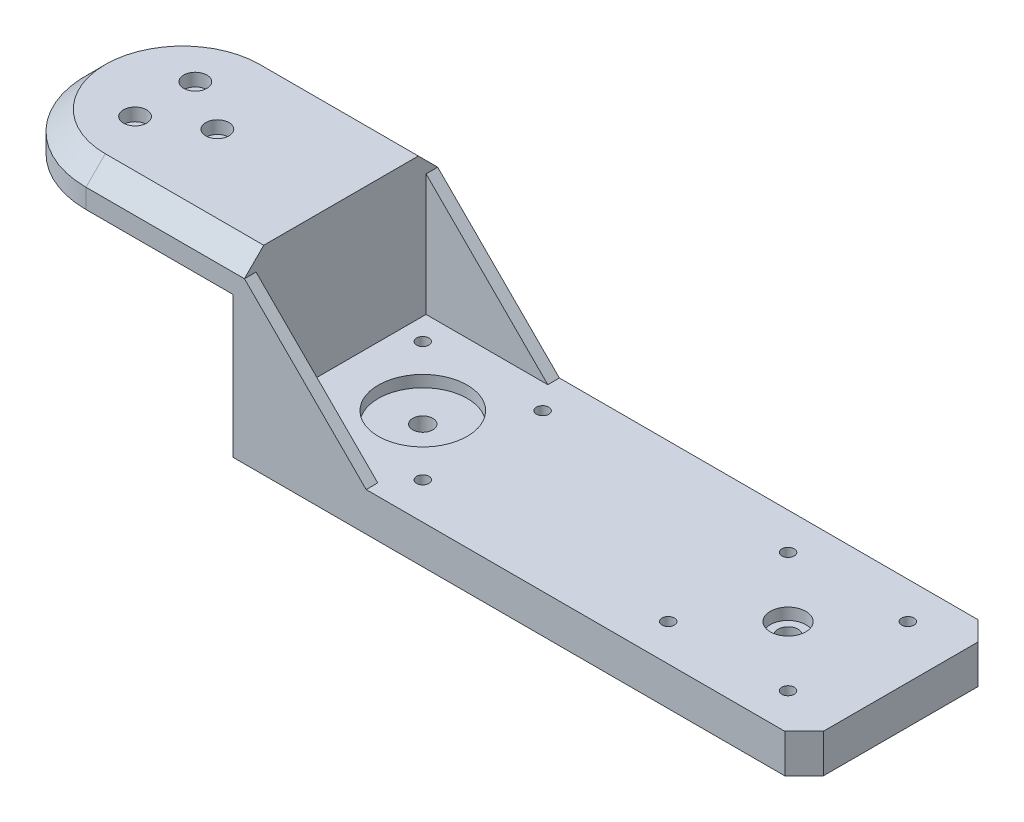
SolidWorks part; units mm, degrees
ref_plane "前视基准面" through (0, 0, 0) normal (0, 0, 1) x (1, 0, 0)
ref_plane "上视基准面" through (0, 0, 0) normal (0, 1, 0) x (1, 0, 0)
ref_plane "右视基准面" through (0, 0, 0) normal (1, 0, 0) x (0, 0, -1)
other "Configuration Table"
sketch "草图1" plane through (0, 0, 0) normal (0, 1, 0) x (1, 0, 0)
  line L0 (0, 0) -> (9, 0) construction
  circle A0 centre (0, 0) radius 12.4
  circle A1 centre (9, 0) radius 1.6
  circle A2 centre (-4.5, -7.7942) radius 1.6
  circle A3 centre (-4.5, 7.7942) radius 1.6
  dimension "D1" = 24.8
  dimension "D2" = 3.2
  dimension "D5" = 9
  dimension "D4" = 3
extrude "凸台-拉伸1" add sketch "草图1" along normal blind 19.5
sketch "草图4" plane through (0, 19.5, 0) normal (0, 1, 0) x (1, 0, 0)
  line L0 (0, 25) -> (33, 25)
  line L1 (33, 25) -> (33, -25)
  line L2 (33, -25) -> (0, -25)
  arc A0 (0, 25) -> (0, -25) centre (0, 0) ccw
  circle A1 centre (0, 0) radius 12.4
  circle A2 centre (0, 0) radius 12.4 construction
  dimension "D1" = 50
  dimension "D2" = 33
extrude "凸台-拉伸3" add sketch "草图4" against normal blind 10
sketch "草图5" plane through (33, 0, 0) normal (1, 0, 0) x (0, 0, -1)
  line L1 (-25, 19.5) -> (25, 19.5)
  line L2 (-25, 19.5) -> (-25, -17)
  line L3 (-25, -17) -> (25, -17)
  line L4 (25, 19.5) -> (25, -17)
  dimension "D1" = 36.5
extrude "凸台-拉伸4" add sketch "草图5" along normal blind 8
sketch "草图6" plane through (0, -17, 0) normal (0, -1, 0) x (1, 0, 0)
  line L0 (41, 25) -> (41, -25) construction
  line L1 (33, 25) -> (185.81, 25)
  line L2 (33, 25) -> (33, -25)
  line L3 (33, -25) -> (185.81, -25)
  line L5 (46.65, 15.5) -> (77.65, 15.5) construction
  line L6 (46.65, 15.5) -> (46.65, -15.5) construction
  line L7 (62.15, 0) -> (62.15, 25) construction
  line L8 (185.81, 25) -> (185.81, -25)
  line L9 (46.65, 15.5) -> (141.16, 15.5) construction
  circle A1 centre (62.15, 0) radius 2.6
  circle A2 centre (156.66, 0) radius 2.6
  circle A3 centre (46.65, 15.5) radius 1.6
  circle A4 centre (77.65, 15.5) radius 1.6
  circle A5 centre (77.65, -15.5) radius 1.6
  circle A6 centre (46.65, -15.5) radius 1.6
  circle A7 centre (141.16, 15.5) radius 1.6
  circle A8 centre (172.16, 15.5) radius 1.6
  circle A9 centre (172.16, -15.5) radius 1.6
  circle A10 centre (141.16, -15.5) radius 1.6
  dimension "D2" = 5.2
  dimension "D3" = 21.15
  dimension "D8" = 15.5
  dimension "D9" = 3.2
  dimension "D10" = 5.2
  dimension "D11" = 94.51
  dimension "D14" = 13.65
  dimension "D6" = 31
  dimension "D7" = 31
  dimension "D13" = 94.51
  dimension "D4" = 2
  dimension "D5" = 2
  dimension "D12" = 2
extrude "凸台-拉伸5" add sketch "草图6" along normal blind 10
sketch "草图7" plane through (0, -17, 0) normal (0, 1, 0) x (1, 0, 0)
  circle A0 centre (156.66, 0) radius 4.6
  circle A1 centre (156.66, 0) radius 2.6 construction
  dimension "D1" = 9.2
extrude "切除-拉伸1" cut sketch "草图7" against normal blind 3
chamfer "倒角2" distance 5 angle 45 3 edges at (20.5, 19.5, -25) (20.5, 19.5, 25) (-25, 19.5, 0)
sketch "草图9" plane through (0, 0, 25) normal (0, 0, 1) x (1, 0, 0)
  line L0 (41, 14.5) -> (72.5, -17)
  line L1 (185.81, -17) -> (41, -17) construction
  line L2 (72.5, -17) -> (41, -17)
  line L3 (41, -17) -> (41, 14.5)
  dimension "D1" = 45
extrude "凸台-拉伸6" add sketch "草图9" against normal blind 3
sketch "草图10" plane through (0, 0, -25) normal (0, 0, -1) x (-1, 0, 0)
  line L3 (-41, -17) -> (-41, 14.5)
  line L4 (-41, 14.5) -> (-72.5, -17)
  line L5 (-72.5, -17) -> (-41, -17)
  line L6 (-41, -17) -> (-41, 14.5)
  line L7 (-41, 14.5) -> (-72.5, -17)
  line L8 (-72.5, -17) -> (-41, -17)
  dimension "D1" = 0
extrude "凸台-拉伸7" add sketch "草图10" against normal blind 3
chamfer "倒角3" distance 5 angle 45 2 edges at (33, -8.75, 25) (33, -8.75, -25)
chamfer "倒角4" distance 5 angle 45 2 edges at (185.81, -22, 25) (185.81, -22, -25)
sketch "草图13" plane through (0, -17, 0) normal (0, 1, 0) x (1, 0, 0)
  circle A0 centre (62.15, 0) radius 11.5
  dimension "D1" = 23
extrude "切除-拉伸3" cut sketch "草图13" against normal blind 3
chamfer "倒角6" distance 1 angle 45 1 edges at (0, 0, 12.4)
sketch "草图18" plane through (0, 19.5, 0) normal (0, 1, 0) x (1, 0, 0)
  circle A0 centre (-4.5, 7.7942) radius 3
  circle A1 centre (-4.5, -7.7942) radius 3
  circle A2 centre (9, 0) radius 3
  dimension "D1" = 6
extrude "切除-拉伸6" cut sketch "草图18" against normal blind 3.3
